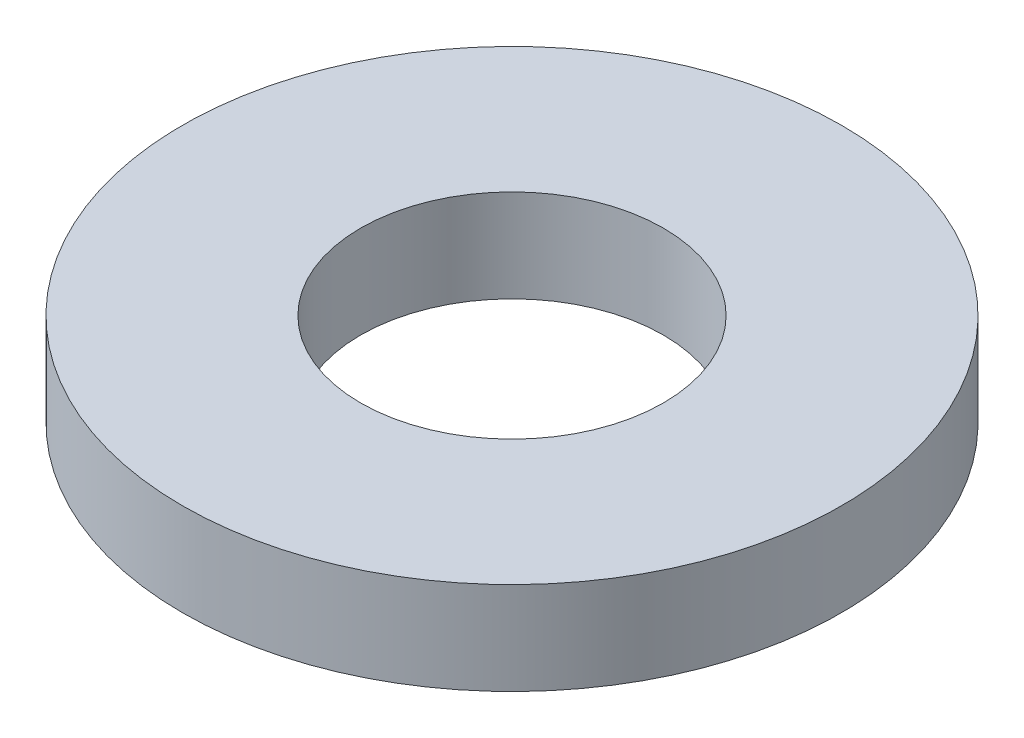
SolidWorks part; units mm, degrees
ref_plane "Front Plane" through (0, 0, 0) normal (0, 0, 1) x (1, 0, 0)
ref_plane "Top Plane" through (0, 0, 0) normal (0, 1, 0) x (1, 0, 0)
ref_plane "Right Plane" through (0, 0, 0) normal (1, 0, 0) x (0, 0, -1)
sketch "Sketch1" plane through (0, 0, 0) normal (0, 1, 0) x (1, 0, 0)
  circle A0 centre (0, 0) radius 92.5
  dimension "FLANGE_OD" = 185
extrude "Boss-Extrude1" add sketch "Sketch1" along normal blind 26
sketch "Sketch2" plane through (0, 0, 0) normal (0, 1, 0) x (1, 0, 0)
  circle A0 centre (0, 0) radius 42.5
  dimension "BORE_D" = 85
extrude "Cut-Extrude1" cut sketch "Sketch2" along normal through all
sketch "Sketch3" plane through (0, 26, 0) normal (0, 1, 0) x (1, 0, 0)
  circle A0 centre (0, 0) radius 27.1149 construction
  circle A1 centre (-27.1149, 0) radius 5.6695
  dimension "BOLT_D" = 11.339
  dimension "BOLT_PCD" = 54.2298
extrude "Cut-Extrude2" cut sketch "Sketch3" against normal blind 23.2119 rebuild error yes
pattern_circular "CirPattern1" count 3 over 360 rebuild error yes
